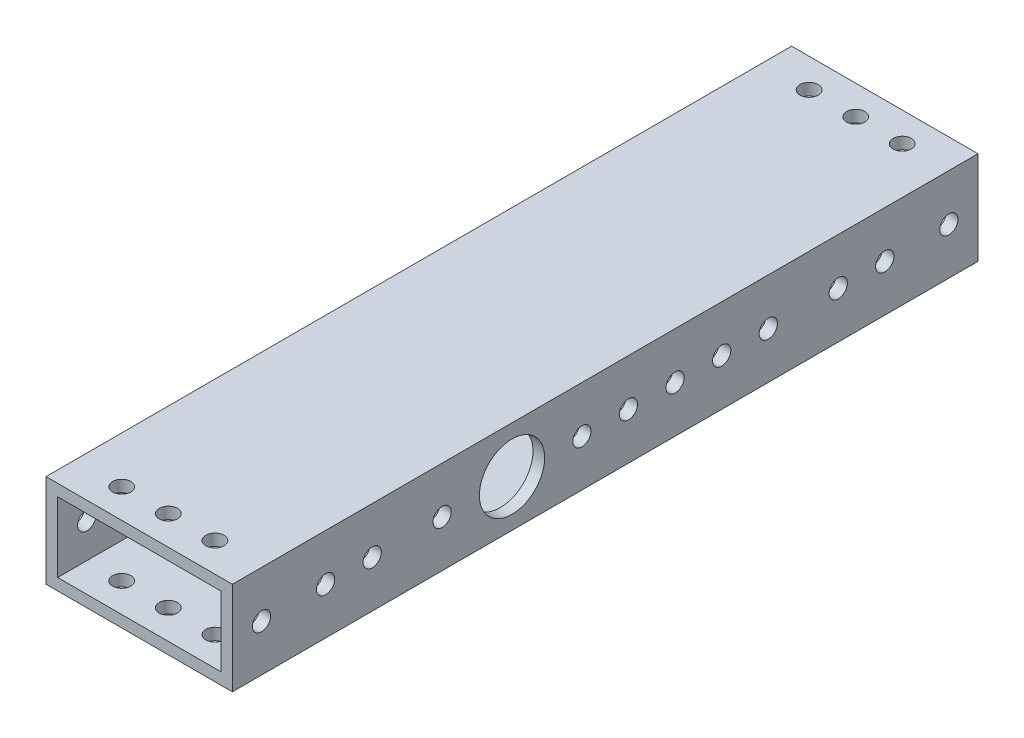
SolidWorks part; units mm, degrees
material "6061-T6 (SS)"
ref_plane "Front Plane" through (0, 0, 0) normal (0, 0, 1) x (1, 0, 0)
ref_plane "Top Plane" through (0, 0, 0) normal (0, 1, 0) x (1, 0, 0)
ref_plane "Right Plane" through (0, 0, 0) normal (1, 0, 0) x (0, 0, -1)
sketch "Sketch1" plane through (0, 0, 0) normal (0, 0, 1) x (1, 0, 0)
  line L0 (-22.225, 9.525) -> (22.225, 9.525)
  line L1 (-25.4, -12.7) -> (25.4, -12.7)
  line L2 (-25.4, -12.7) -> (-25.4, 12.7)
  line L3 (-25.4, 12.7) -> (25.4, 12.7)
  line L4 (25.4, -12.7) -> (25.4, 12.7)
  line L5 (-25.4, -12.7) -> (25.4, 12.7) construction
  line L6 (-25.4, 12.7) -> (25.4, -12.7) construction
  line L7 (22.225, -9.525) -> (22.225, 9.525)
  line L8 (-22.225, -9.525) -> (22.225, -9.525)
  line L9 (-22.225, -9.525) -> (-22.225, 9.525)
  point P0 (0, 0)
  dimension "D1" = 50.8
  dimension "D2" = 25.4
  dimension "D3" = 3.175
extrude "Boss-Extrude1" add sketch "Sketch1" along normal mid plane 203.2
sketch "Sketch3" plane through (0, 12.7, 0) normal (0, 1, 0) x (1, 0, 0)
  line L0 (-25.4, 0) -> (25.4, 0) construction
  line L1 (-25.4, -101.6) -> (-25.4, 101.6) construction
  line L2 (25.4, -101.6) -> (25.4, 101.6) construction
  line L3 (25.4, -101.6) -> (-25.4, -101.6) construction
  circle A0 centre (-12.7, -93.6625) radius 2.4892
  circle A1 centre (0, -93.6625) radius 2.4892
  circle A2 centre (12.7, -93.6625) radius 2.4892
  circle A3 centre (12.7, 93.6625) radius 2.4892
  circle A4 centre (0, 93.6625) radius 2.4892
  circle A5 centre (-12.7, 93.6625) radius 2.4892
  dimension "D1" = 4.9784
  dimension "D2" = 12.7
  dimension "D3" = 12.7
  dimension "D4" = 7.9375
extrude "Cut-Extrude2" cut sketch "Sketch3" against normal through all
sketch "Sketch4" plane through (25.4, 0, 0) normal (1, 0, 0) x (0, 0, -1)
  line L0 (-25.4, 0) -> (-45.1908, 0) construction
  line L1 (-16.51, 0) -> (-34.29, 0) construction
  line L8 (-25.4, 0) -> (31.75, 0) construction
  line L9 (0, 12.7) -> (0, -12.7) construction
  line L10 (-101.6, 12.7) -> (101.6, 12.7) construction
  line L11 (-101.6, -12.7) -> (101.6, -12.7) construction
  circle A0 centre (-25.4, 0) radius 8.89
  circle A9 centre (31.75, 0) radius 2.4892
  circle A10 centre (19.05, 0) radius 2.4892
  dimension "D2" = 17.78
  dimension "D3" = 25.4
  dimension "D1" = 57.15
  dimension "D4" = 4.9784
  dimension "D6" = 44.45
extrude "Cut-Extrude3" cut sketch "Sketch4" against normal through all contours A0 | A9 | A10
sketch "Sketch2" plane through (25.4, 0, 0) normal (1, 0, 0) x (0, 0, -1)
  line L0 (-101.6, -12.7) -> (-101.6, 12.7) construction
  line L1 (0, 12.7) -> (0, -12.7) construction
  line L2 (-101.6, 12.7) -> (101.6, 12.7) construction
  line L3 (-101.6, -12.7) -> (101.6, -12.7) construction
  circle A0 centre (-93.6625, 0) radius 2.4892
  circle A1 centre (93.6625, 0) radius 2.4892
  circle A2 centre (-76.2, 0) radius 2.4892
  circle A3 centre (-63.5, 0) radius 2.4892
  circle A4 centre (63.5, 0) radius 2.4892
  circle A5 centre (76.2, 0) radius 2.4892
  dimension "D2" = 4.9784
  dimension "D5" = 4.9784
  dimension "D4" = 25.4
  dimension "D1" = 7.9375
  dimension "D3" = 12.7
extrude "Cut-Extrude1" cut sketch "Sketch2" against normal through all
sketch "Sketch5" plane through (0, -12.7, 0) normal (0, -1, 0) x (1, 0, 0)
  line L0 (-25.4, 101.6) -> (-25.4, -101.6) construction
  line L1 (-25.4, 101.6) -> (25.4, 101.6) construction
  line L4 (25.4, 22.225) -> (-25.4, 22.225) construction
  line L5 (25.4, 101.6) -> (25.4, -101.6) construction
  circle A0 centre (-3.175, 66.675) radius 2.4892
  circle A1 centre (-15.875, 66.675) radius 2.4892
  circle A2 centre (-15.875, 53.975) radius 2.4892
  circle A3 centre (-3.175, 53.975) radius 2.4892
  circle A8 centre (-3.175, -9.525) radius 2.4892
  circle A9 centre (-15.875, -9.525) radius 2.4892
  circle A10 centre (-15.875, -22.225) radius 2.4892
  circle A11 centre (-3.175, -22.225) radius 2.4892
  dimension "D3" = 4.9784
  dimension "D4" = 9.525
  dimension "D7" = 12.7
  dimension "D12" = 79.375
  dimension "D5" = 31.75
  dimension "D6" = 12.7
  dimension "D1" = 2
  dimension "D2" = 2
extrude "Cut-Extrude4" cut sketch "Sketch5" against normal up to next
sketch "Sketch7" plane through (25.4, 0, 0) normal (1, 0, 0) x (0, 0, -1)
  circle A0 centre (44.45, 0) radius 2.4892
  circle A1 centre (31.75, 0) radius 2.4892 construction
  circle A5 centre (6.35, 0) radius 2.4892
  circle A6 centre (-6.35, 0) radius 2.4892
  circle A7 centre (-44.45, 0) radius 2.4892
  circle A8 centre (-25.4, 0) radius 8.89 construction
  dimension "D1" = 12.7
  dimension "D2" = 19.05
  dimension "D3" = 19.05
  dimension "D4" = 12.7
extrude "Cut-Extrude5" cut sketch "Sketch7" against normal up to next contours A0 | A7 | A6 | A5
